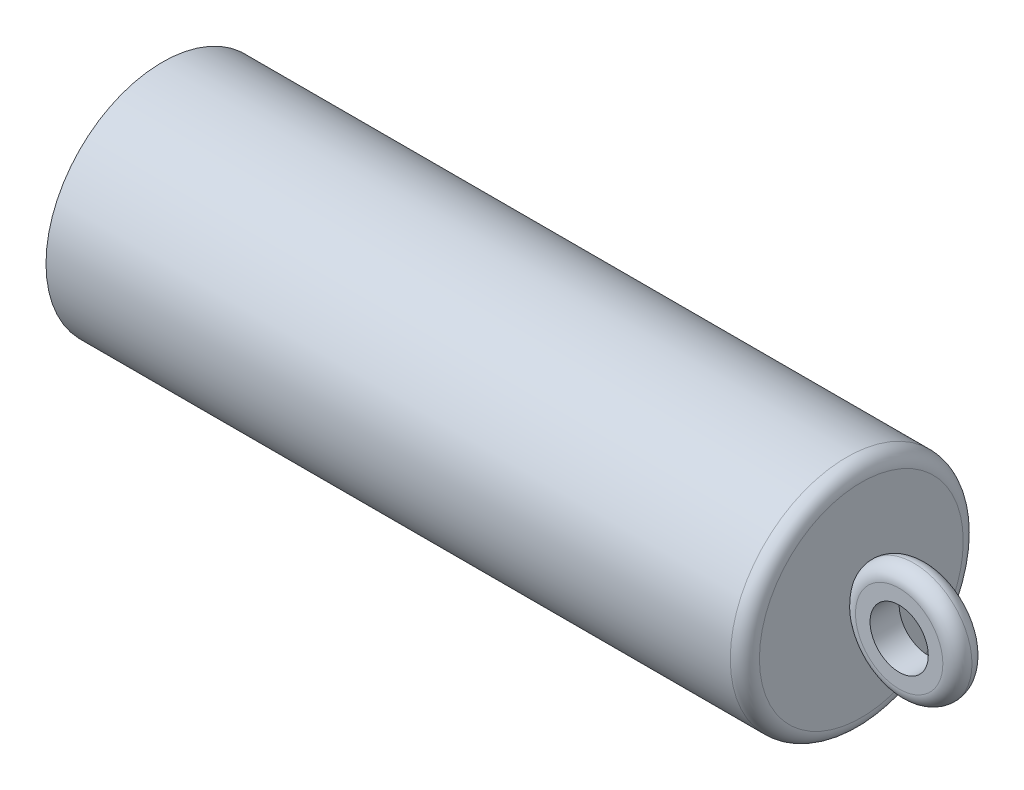
SolidWorks part; units mm, degrees
material "CMR DEFAULT - CHANGE MATERIAL"
ref_plane "XY PLANE - TOP" through (0, 0, 0) normal (0, 0, 1) x (1, 0, 0)
ref_plane "XZ PLANE - SIDE" through (0, 0, 0) normal (0, 1, 0) x (1, 0, 0)
ref_plane "YZ PLANE - FRONT" through (0, 0, 0) normal (1, 0, 0) x (0, 0, -1)
sketch "Sketch1" plane through (0, 0, 0) normal (1, 0, 0) x (0, 0, -1)
  circle A0 centre (0, 0) radius 12.7
  dimension "D1" = 25.4
extrude "Boss-Extrude1" add sketch "Sketch1" along normal blind 76.2
shell "Shell3" thickness 6.35 removed face at (0, 0, -12.7)
sketch "Sketch2" plane through (0, 0, 0) normal (0, 0, 1) x (1, 0, 0)
  line L0 (88.5065, 0) -> (-88.5065, 0) construction
  line L1 (76.2, -12.7) -> (76.2, 12.7) construction
  circle A0 centre (81.915, 0) radius 6.35
  circle A1 centre (81.915, 0) radius 3.175
  dimension "D1" = 12.7
  dimension "D3" = 6.35
  dimension "D2" = 5.715
extrude "Boss-Extrude2" add sketch "Sketch2" along normal mid plane 3.175
fillet "Fillet1" radius 1.5875 2 edges at (88.265, 0, -1.5875) (88.265, 0, 1.5875)
fillet "Fillet2" radius 1.5875 1 edges at (76.2, 0, -12.7)
